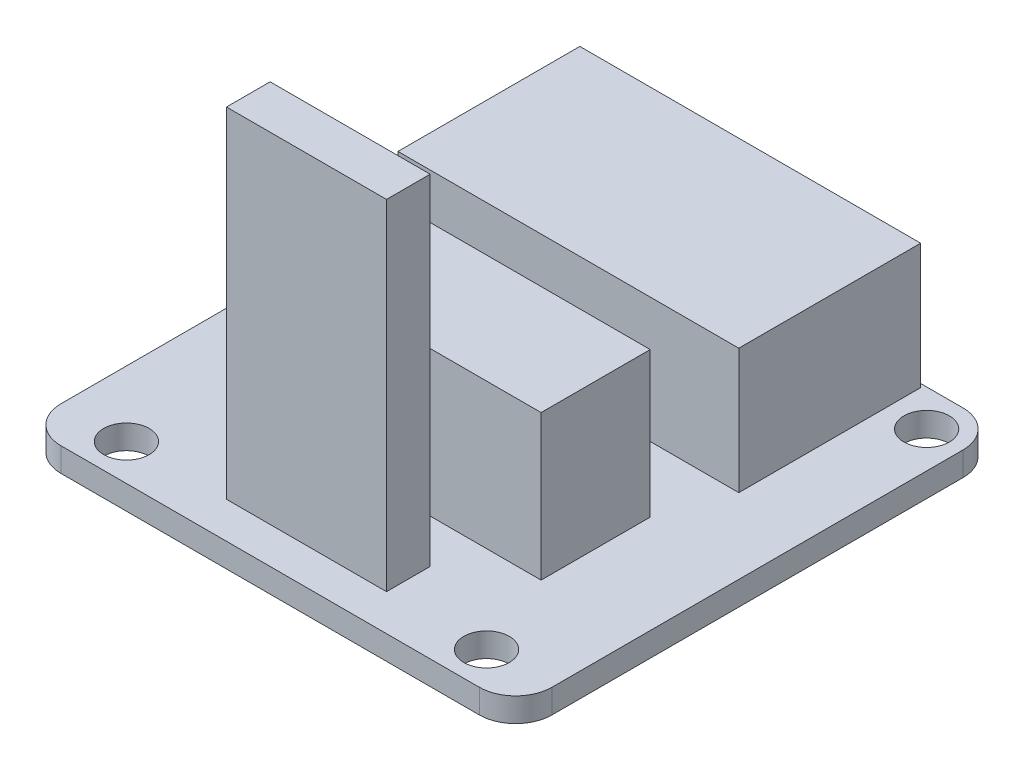
SolidWorks part; units mm, degrees
ref_plane "Front Plane" through (0, 0, 0) normal (0, 0, 1) x (1, 0, 0)
ref_plane "Top Plane" through (0, 0, 0) normal (0, 1, 0) x (1, 0, 0)
ref_plane "Right Plane" through (0, 0, 0) normal (1, 0, 0) x (0, 0, -1)
sketch "Sketch1" plane through (0, 0, 0) normal (0, 1, 0) x (1, 0, 0)
  line L0 (0, -16.891) -> (0, 16.891) construction
  line L1 (-14.605, -16.891) -> (14.605, -16.891)
  line L2 (-17.145, -14.351) -> (-17.145, 14.351)
  line L3 (-14.605, 16.891) -> (14.605, 16.891)
  line L4 (17.145, -14.351) -> (17.145, 14.351)
  line L5 (-17.145, -16.891) -> (17.145, 16.891) construction
  line L6 (-17.145, 16.891) -> (17.145, -16.891) construction
  line L7 (-11.8999, 16.637) -> (11.8999, 16.637)
  line L8 (-11.8999, 16.637) -> (-11.8999, 3.937)
  line L9 (-11.8999, 3.937) -> (11.8999, 3.937)
  line L10 (11.8999, 16.637) -> (11.8999, 3.937)
  line L12 (-10.287, -8.255) -> (10.287, -8.255)
  line L13 (-10.287, -8.255) -> (-10.287, -0.635)
  line L14 (-10.287, -0.635) -> (10.287, -0.635)
  line L15 (10.287, -8.255) -> (10.287, -0.635)
  line L16 (-10.287, -8.255) -> (10.287, -0.635) construction
  line L17 (-10.287, -0.635) -> (10.287, -8.255) construction
  line L18 (-5.588, -14.351) -> (5.588, -14.351)
  line L19 (-5.588, -14.351) -> (-5.588, -11.303)
  line L20 (-5.588, -11.303) -> (5.588, -11.303)
  line L21 (5.588, -14.351) -> (5.588, -11.303)
  line L22 (-5.588, -14.351) -> (5.588, -11.303) construction
  line L23 (-5.588, -11.303) -> (5.588, -14.351) construction
  circle A0 centre (-14.605, 14.351) radius 1.5875
  circle A1 centre (-12.573, -14.351) radius 1.5875
  circle A2 centre (12.573, -14.351) radius 1.5875
  circle A3 centre (14.605, 14.351) radius 1.5875
  arc A4 (14.605, -16.891) -> (17.145, -14.351) centre (14.605, -14.351) ccw
  arc A5 (-14.605, -16.891) -> (-17.145, -14.351) centre (-14.605, -14.351) cw
  arc A6 (14.605, 16.891) -> (17.145, 14.351) centre (14.605, 14.351) cw
  arc A7 (-17.145, 14.351) -> (-14.605, 16.891) centre (-14.605, 14.351) cw
  point P0 (0, 0)
  point P30 (0, 3.937)
  point P33 (0, 0)
  point P34 (0, -4.445)
  point P39 (0, -12.827)
  dimension "D3" = 3.175
  dimension "D12" = 2.54
  dimension "D1" = 33.782
  dimension "D2" = 34.29
  dimension "D4" = 2.54
  dimension "D5" = 2.54
  dimension "D6" = 2.54
  dimension "D7" = 2.54
  dimension "D8" = 4.572
  dimension "D9" = 2.54
  dimension "D10" = 2.54
  dimension "D11" = 4.572
  dimension "D13" = 23.7998
  dimension "D14" = 0.254
  dimension "D15" = 12.7
  dimension "D16" = 7.62
  dimension "D17" = 20.574
  dimension "D18" = 25.146
  dimension "D19" = 3.048
  dimension "D20" = 11.176
  dimension "D21" = 2.54
extrude "Boss-Extrude1" add sketch "Sketch1" along normal blind 1.6764 contours L18 L21 L20 L19 | L12 L15 L14 L13 | L10 L7 L8 L9 | A7 L2 A5 L1 A4 L4 A6 L3 A3 A2 A1 A0 L21 L18 L19 L20 L15 L12 L13 L14 L7 L10 L9 L8 region at (-16.0607, 0, 15.8067) region at (0, 0, -10.287) region at (0, 0, 4.445) region at (0, 0, 12.827)
extrude "Boss-Extrude2" add sketch "Sketch1<3>" along normal blind 10.414 contours L8 L9 L10 L7
sketch "Sketch1<3>" plane through (0, 0, 0) normal (0, 1, 0) x (1, 0, 0) same geometry as "Sketch1"
extrude "Boss-Extrude3" add sketch "Sketch1<4>" along normal blind 11.811 contours L12 L15 L14 L13 region at (0, 0, 4.445)
sketch "Sketch1<4>" plane through (0, 0, 0) normal (0, 1, 0) x (1, 0, 0) same geometry as "Sketch1"
extrude "Boss-Extrude4" add sketch "Sketch1<5>" along normal blind 25.4 contours L18 L21 L20 L19
sketch "Sketch1<5>" plane through (0, 0, 0) normal (0, 1, 0) x (1, 0, 0) same geometry as "Sketch1"
